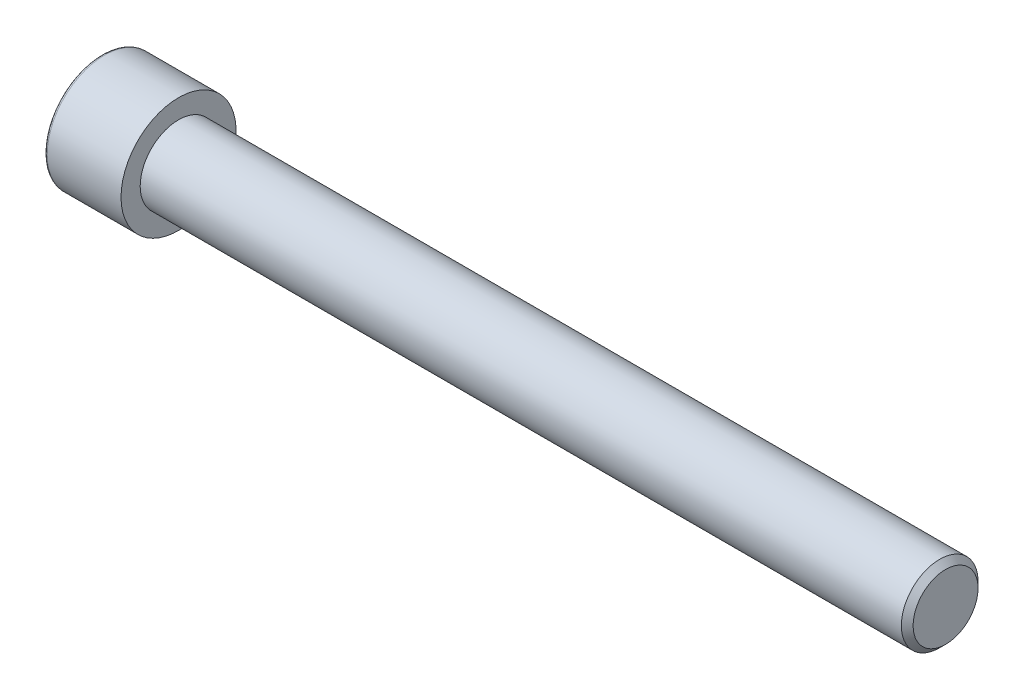
SolidWorks part; units mm, degrees
ref_plane "Płaszczyzna przednia" through (0, 0, 0) normal (0, 0, 1) x (1, 0, 0)
ref_plane "Płaszczyzna górna" through (0, 0, 0) normal (0, 1, 0) x (1, 0, 0)
ref_plane "Płaszczyzna prawa" through (0, 0, 0) normal (1, 0, 0) x (0, 0, -1)
sketch "Szkic1" plane through (0, 0, 0) normal (0, 0, 1) x (1, 0, 0)
  line L0 (0, 0) -> (0, 12)
  line L1 (0, 12) -> (16, 12)
  line L2 (16, 12) -> (16, 0)
  line L3 (16, 0) -> (0, 0)
  line L4 (16, 0) -> (0, 0) construction
revolve "Obrót1" add sketch "Szkic1" angle 360 about L4 reverse direction yes
sketch "Szkic2" plane through (0, 0, 0) normal (0, 0, 1) x (1, 0, 0)
  line L0 (0, 12) -> (0, 11.4)
  line L1 (0.6, 12) -> (0, 12)
  line L2 (16, 0) -> (0, 0) construction
  arc A0 (0, 11.4) -> (0.6, 12) centre (0.6, 11.4) cw
revolve "Wycięcie-obrót1" cut sketch "Szkic2" angle 360 about L2 reverse direction yes
sketch "Szkic3" plane through (0, 0, 0) normal (0, 0, 1) x (1, 0, 0)
  line L0 (16, 0) -> (16, 8)
  line L1 (16, 8) -> (174.773, 8)
  line L2 (174.773, 8) -> (176, 6.773)
  line L3 (176, 6.773) -> (176, 0)
  line L4 (176, 0) -> (16, 0)
  line L5 (176, 0) -> (16, 0) construction
revolve "Obrót2" add sketch "Szkic3" angle 360 about L5 reverse direction yes
cosmetic thread "Oznaczenie gwintu1" parameters "D1"=44, "D2"=13.546
sketch "Szkic4" plane through (0, 0, 0) normal (0, 0, 1) x (1, 0, 0)
  line L0 (0, 0) -> (0, 8.5)
  line L1 (0, 8.5) -> (8, 8.5)
  line L2 (8, 8.5) -> (12.9075, 0)
  line L3 (12.9075, 0) -> (0, 0)
  line L4 (12.9075, 0) -> (0, 0) construction
revolve "Wycięcie-obrót2" cut sketch "Szkic4" angle 360 about L4 reverse direction yes
sketch "Szkic5" plane through (0, 0, 0) normal (1, 0, 0) x (0, 0, -1)
  line L0 (-7, 4.0415) -> (-7, -4.0415)
  line L1 (-7, -4.0415) -> (0, -8.0829)
  line L2 (0, -8.0829) -> (7, -4.0415)
  line L3 (7, -4.0415) -> (7, 4.0415)
  line L4 (7, 4.0415) -> (0, 8.0829)
  line L5 (0, 8.0829) -> (-7, 4.0415)
  circle A0 centre (0, 0) radius 9
extrude "Dodanie-wyciągnięcie1" add sketch "Szkic5" along normal blind 12
ref_plane "Płaszczyzna1" through (16, 0, 0) normal (1, 0, 0) x (0, 0, -1)
ref_plane "IP2 XY" through (16, 0, 0) normal (-1, 0, 0) x (0, 0, 1)
ref_plane "IP2 XZ" through (0, 0, 0) normal (0, 1, 0) x (1, 0, 0)
ref_plane "IP2 YZ" through (0, 0, 0) normal (0, 0, -1) x (-1, 0, 0)
ref_axis "IP2 X" through (16, 0, 80.9) along (0, 0, -1)
ref_axis "IP2 Y" through (16, 50, 0) along (0, -1, 0)
ref_axis "IP2 Z" through (-80.9, 0, 0) along (1, 0, 0)
sketch3d "IP2"
  point P0 (16, 0, 0)
